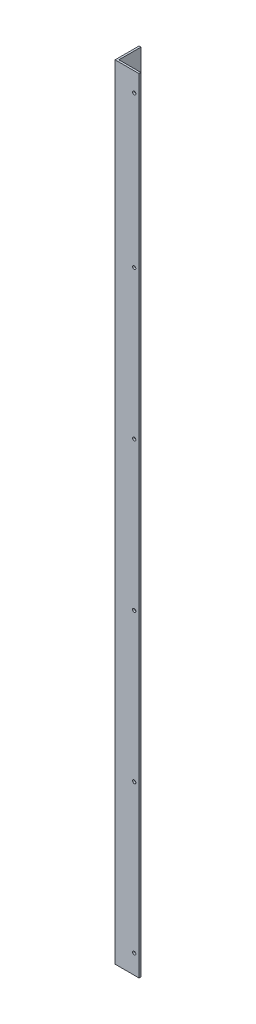
SolidWorks part; units mm, degrees
material "6063-O"
ref_plane "Piano frontale" through (0, 0, 0) normal (0, 0, 1) x (1, 0, 0)
ref_plane "Piano superiore" through (0, 0, 0) normal (0, 1, 0) x (1, 0, 0)
ref_plane "Piano destro" through (0, 0, 0) normal (1, 0, 0) x (0, 0, -1)
sketch "Schizzo2" plane through (0, 0, 0) normal (0, 1, 0) x (1, 0, 0)
  line L0 (0, 0) -> (25, 0)
  line L1 (25, 0) -> (25, 2)
  line L2 (25, 2) -> (2, 2)
  line L3 (2, 2) -> (2, 25)
  line L4 (2, 25) -> (0, 25)
  line L5 (0, 25) -> (0, 0)
  dimension "D1" = 25
  dimension "D2" = 25
  dimension "D3" = 2
  dimension "D4" = 2
extrude "Estrusione-Estrusione1" add sketch "Schizzo2" along normal blind 819
sketch "Schizzo3" plane through (0, 0, 0) normal (0, 0, 1) x (1, 0, 0)
  line L0 (20, 843.1808) -> (20, -52.7752) construction
  line L1 (0, 819) -> (0, 0) construction
  line L2 (0, 0) -> (25, 0) construction
  circle A0 centre (20, 20) radius 1.7
  circle A1 centre (20, 330.4) radius 1.7
  circle A2 centre (20, 485.6) radius 1.7
  circle A3 centre (20, 175.2) radius 1.7
  circle A4 centre (20, 640.8) radius 1.7
  circle A5 centre (20, 799) radius 1.7
  dimension "D4" = 330.4
  dimension "D8" = 3.4
  dimension "D1" = 20
  dimension "D2" = 20
  dimension "D3" = 175.2
  dimension "D5" = 485.6
  dimension "D6" = 640.8
  dimension "D7" = 799
extrude "Taglio-Estrusione1" cut sketch "Schizzo3" against normal through all
